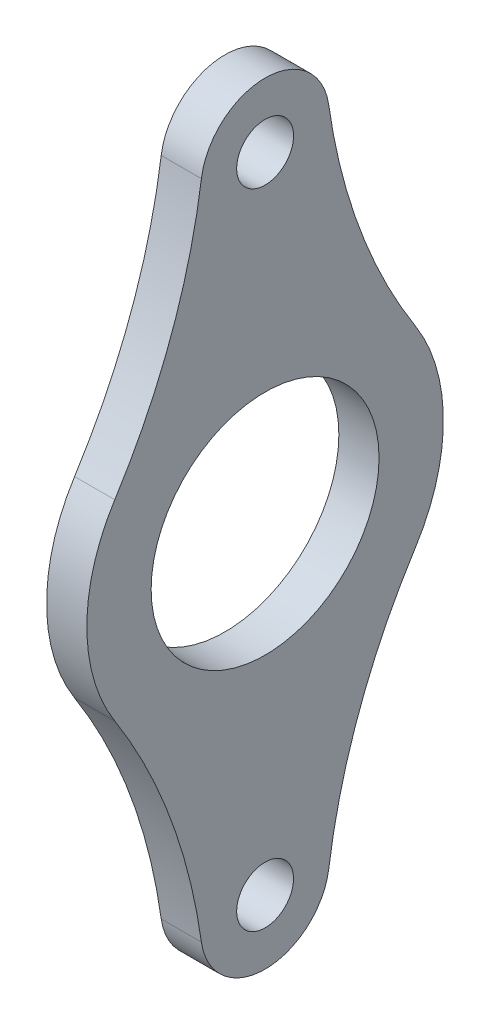
SolidWorks part; units mm, degrees
material "6061-T6 (SS)"
ref_plane "Front Plane" through (0, 0, 0) normal (0, 0, 1) x (1, 0, 0)
ref_plane "Top Plane" through (0, 0, 0) normal (0, 1, 0) x (1, 0, 0)
ref_plane "Right Plane" through (0, 0, 0) normal (1, 0, 0) x (0, 0, -1)
ref_plane "Plane1" through (47.188, 0, 0) normal (-1, 0, 0) x (0, 0, 1)
sketch "Sketch1" plane through (47.188, 0, 0) normal (-1, 0, 0) x (0, 0, 1)
  line L0 (-51.1134, 32.5835) -> (-5.0306, 26.107) construction
  line L1 (-23.0873, 0) -> (0, 0) construction
  line L2 (0, 0) -> (0, 25.4) construction
  circle A0 centre (0, -25.4) radius 2.2479 construction
  circle A1 centre (0, 25.4) radius 2.2479 construction
  circle A2 centre (0, -25.4) radius 2.2479
  circle A3 centre (0, 25.4) radius 2.2479
  circle A4 centre (0, 0) radius 9
  circle A5 centre (0, 0) radius 6 construction
  arc A6 (-11.8728, 7.5686) -> (-11.8728, -7.5686) centre (0, 0) ccw
  arc A7 (5.0306, 26.107) -> (-5.0306, 26.107) centre (0, 25.4) ccw
  arc A8 (-5.0306, -26.107) -> (5.0306, -26.107) centre (0, -25.4) ccw
  arc A9 (-5.0306, 26.107) -> (-11.8728, 7.5686) centre (-51.1134, 32.5835) cw
  arc A10 (5.0306, 26.107) -> (11.8728, 7.5686) centre (51.1134, 32.5835) ccw
  arc A11 (5.0306, -26.107) -> (11.8728, -7.5686) centre (51.1134, -32.5835) cw
  arc A12 (-5.0306, -26.107) -> (-11.8728, -7.5686) centre (-51.1134, -32.5835) ccw
  arc A13 (11.8728, -7.5686) -> (11.8728, 7.5686) centre (0, 0) ccw
  dimension "D1" = 18
  dimension "D2" = 12
  dimension "D4" = 10.16
  dimension "D3" = 5.08
  dimension "D5" = 8
extrude "Boss-Extrude1" add sketch "Sketch1" along normal blind 3.175
equation "\"D1@Sketch1\"=18mm"
equation "\"D2@Sketch1\"=12mm"
